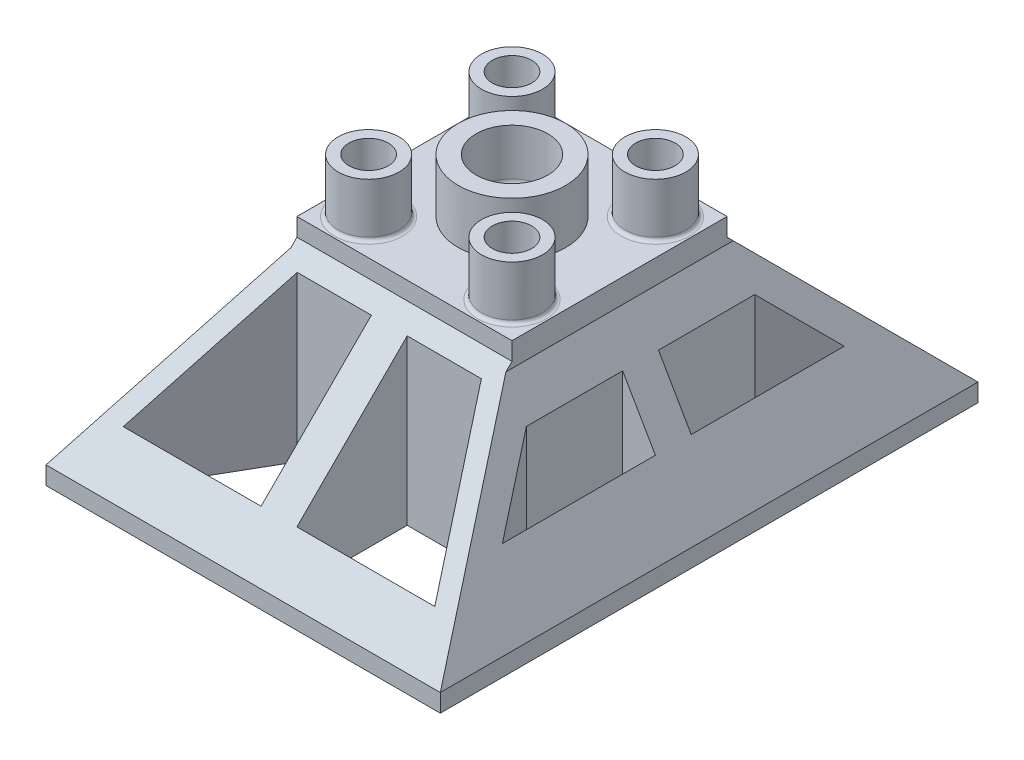
SolidWorks part; units mm, degrees
ref_plane "前基準面" through (0, 0, 0) normal (0, 0, 1) x (1, 0, 0)
ref_plane "上基準面" through (0, 0, 0) normal (0, 1, 0) x (1, 0, 0)
ref_plane "右基準面" through (0, 0, 0) normal (1, 0, 0) x (0, 0, -1)
sketch "草圖1" plane through (0, 0, 0) normal (0, 1, 0) x (1, 0, 0)
  line L0 (-1000, 0) -> (49000, 0) construction
  line L1 (-30, -30) -> (30, -30)
  line L2 (-30, -30) -> (-30, 30)
  line L3 (-30, 30) -> (30, 30)
  line L4 (30, -30) -> (30, 30)
  line L5 (-30, -30) -> (30, 30) construction
  line L6 (-30, 30) -> (30, -30) construction
  line L7 (0, -1000) -> (0, 49000) construction
  circle A0 centre (20, 20) radius 5.5
  circle A1 centre (-20, 20) radius 5.5
  circle A2 centre (20, -20) radius 5.5
  circle A3 centre (-20, -20) radius 5.5
  point P0 (0, 0)
  dimension "D4" = 11
  dimension "D1" = 60
  dimension "D2" = 60
  dimension "D3" = 10
  dimension "D5" = 10
extrude "填料-伸長1" add sketch "草圖1" along normal blind 7
sketch "草圖2" plane through (0, 7, 0) normal (0, 1, 0) x (1, 0, 0)
  line L0 (-1000, 0) -> (49000, 0) construction
  line L1 (0, -1000) -> (0, 49000) construction
  circle A0 centre (-20, -20) radius 5.5 construction
  circle A1 centre (20, -20) radius 5.5 construction
  circle A2 centre (20, 20) radius 5.5 construction
  circle A3 centre (-20, 20) radius 5.5 construction
  circle A4 centre (-20, -20) radius 5.5
  circle A5 centre (20, -20) radius 5.5
  circle A6 centre (20, 20) radius 5.5
  circle A7 centre (-20, 20) radius 5.5
  circle A8 centre (-20, 20) radius 8.5
  circle A9 centre (20, 20) radius 8.5
  circle A10 centre (20, -20) radius 8.5
  circle A11 centre (-20, -20) radius 8.5
  circle A12 centre (0, 0) radius 15
  dimension "D1" = 3
  dimension "D2" = 30
extrude "填料-伸長2" add sketch "草圖2" along normal blind 15
sketch "草圖3" plane through (0, 0, 0) normal (0, -1, 0) x (1, 0, 0)
  line L1 (-30, 30) -> (30, 30)
  line L2 (-30, 30) -> (-30, -30)
  line L3 (-30, -30) -> (30, -30)
  line L4 (30, 30) -> (30, -30)
extrude "填料-伸長3" add sketch "草圖3" along normal blind 48
sketch "草圖5" plane through (0, -48, 0) normal (0, -1, 0) x (1, 0, 0)
  line L5 (-55, -75) -> (55, -75)
  line L6 (-55, -75) -> (-55, 75)
  line L7 (-55, 75) -> (55, 75)
  line L8 (55, -75) -> (55, 75)
  line L9 (-55, -75) -> (55, 75) construction
  line L10 (-55, 75) -> (55, -75) construction
  point P0 (0, 0)
  dimension "D1" = 110
  dimension "D2" = 150
extrude "填料-伸長4" add sketch "草圖5" against normal blind 5
sketch "草圖4" plane through (0, 7, 0) normal (0, 1, 0) x (1, 0, 0)
  circle A0 centre (0, 0) radius 10
  dimension "D1" = 20
extrude "除料-伸長1" cut sketch "草圖4" against normal through all both and the other way through all
fillet "圓角1" radius 1 4 edges at (20, 7, 11.5) (20, 7, -28.5) (-20, 7, -28.5) (-20, 7, 11.5)
fillet "圓角4" radius 10 1 edges at (0, -48, 10)
sketch "草圖6" plane through (0, -48, 0) normal (0, 1, 0) x (1, 0, 0)
  circle A0 centre (0, 0) radius 7.5
  circle A1 centre (0, 0) radius 10
  dimension "D1" = 15
extrude "填料-伸長5" add sketch "草圖6" along normal blind 5 from offset 50
fillet "圓角5" radius 2 2 edges at (0, 2, 10) (0, 7, 10)
chamfer "導角1" distance 45 angle 45 2 edges at (0, -43, 30) (0, -43, -30)
chamfer "導角2" distance 25 angle 60 2 edges at (-30, -43, 0) (30, -43, 0) first distance on face at (-42.5, -43, 0) first distance on face at (42.5, -43, 0)
sketch "草圖7" plane through (0, -48, 0) normal (0, -1, 0) x (1, 0, 0)
  line L0 (0, 0) -> (0, -86.4538) construction
  line L1 (-76.1642, 0) -> (114.3524, 0) construction
  line L60 (-43.453, -65) -> (-25.6881, -34.2304)
  line L61 (-25.6881, -34.2304) -> (-5, -34.2304)
  line L62 (-5, -34.2304) -> (-5, -65)
  line L63 (-5, -65) -> (-43.453, -65)
  line L64 (-45, -47.6795) -> (-35.8659, -31.8587)
  line L65 (-35.8659, -31.8587) -> (-35.8659, -5)
  line L66 (-35.8659, -5) -> (-45, -5)
  line L67 (-45, -5) -> (-45, -47.6795)
  line L68 (-55, 75) -> (-55, -75) construction
  line L69 (-55, -75) -> (55, -75) construction
  line L70 (-55, -75) -> (-30, -31.6987) construction
  line L71 (35.8659, -5) -> (45, -5)
  line L72 (35.8659, -31.8587) -> (35.8659, -5)
  line L73 (45, -47.6795) -> (35.8659, -31.8587)
  line L74 (45, -5) -> (45, -47.6795)
  line L75 (5, -34.2304) -> (5, -65)
  line L76 (25.6881, -34.2304) -> (5, -34.2304)
  line L77 (43.453, -65) -> (25.6881, -34.2304)
  line L78 (5, -65) -> (43.453, -65)
  line L79 (-35.8659, 5) -> (-45, 5)
  line L80 (-35.8659, 31.8587) -> (-35.8659, 5)
  line L81 (-45, 47.6795) -> (-35.8659, 31.8587)
  line L82 (-45, 5) -> (-45, 47.6795)
  line L83 (-5, 34.2304) -> (-5, 65)
  line L84 (-25.6881, 34.2304) -> (-5, 34.2304)
  line L85 (-43.453, 65) -> (-25.6881, 34.2304)
  line L86 (-5, 65) -> (-43.453, 65)
  line L87 (35.8659, 31.8587) -> (35.8659, 5)
  line L88 (45, 47.6795) -> (35.8659, 31.8587)
  line L89 (45, 5) -> (45, 47.6795)
  line L90 (35.8659, 5) -> (45, 5)
  line L91 (25.6881, 34.2304) -> (5, 34.2304)
  line L92 (43.453, 65) -> (25.6881, 34.2304)
  line L93 (5, 65) -> (43.453, 65)
  line L94 (5, 34.2304) -> (5, 65)
  point P17 (-34.7923, -29.2522)
  dimension "D1" = 10
  dimension "D2" = 10
  dimension "D3" = 10
  dimension "D4" = 10
  dimension "D5" = 5
  dimension "D6" = 5
extrude "除料-伸長2" cut sketch "草圖7" against normal through all
